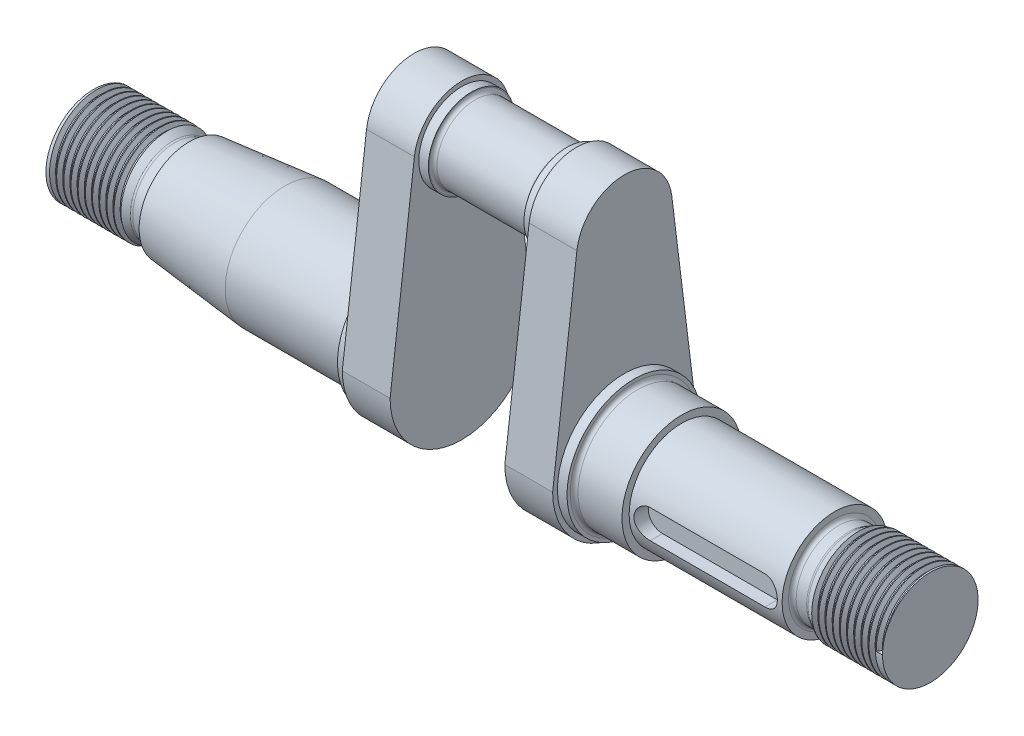
SolidWorks part; units mm, degrees
ref_plane "Ön Düzlem" through (0, 0, 0) normal (0, 0, 1) x (1, 0, 0)
ref_plane "Üst Düzlem" through (0, 0, 0) normal (0, 1, 0) x (1, 0, 0)
ref_plane "Sağ Düzlem" through (0, 0, 0) normal (1, 0, 0) x (0, 0, -1)
sketch "Çizim1" plane through (0, 0, 0) normal (0, 0, 1) x (1, 0, 0)
  line L0 (127.617, 0) -> (-127.617, 0) construction
  line L1 (0, 73.5371) -> (0, -73.5371) construction
  line L2 (-67, 0) -> (-67, 10)
  line L3 (-67, 0) -> (-67, 10)
  line L4 (-67, 10.5) -> (-47, 10.5) construction
  line L5 (-67, 10) -> (-52.2, 10)
  line L6 (-52.2, 10) -> (-50.3938, 8.9572)
  line L7 (-47, 10.5) -> (-47, 9.65)
  line L8 (-49.9938, 8.85) -> (-47.8, 8.85)
  line L9 (-67, 0) -> (0, 0)
  line L10 (-47, 10.5) -> (-27, 12.5)
  line L12 (-27, 12.5) -> (-2.8, 12.5)
  line L13 (0, 14) -> (-2, 14)
  line L14 (-2, 14) -> (-2, 13.3)
  line L15 (0, 14) -> (0, 0)
  arc A0 (-47.8, 8.85) -> (-47, 9.65) centre (-47.8, 9.65) ccw
  arc A1 (-49.9938, 8.85) -> (-50.3938, 8.9572) centre (-49.9938, 9.65) cw
  arc A2 (-2.8, 12.5) -> (-2, 13.3) centre (-2.8, 13.3) ccw
  point P4 (0, 0)
  point P8 (0, 0)
  point P19 (-50.2081, 8.85)
  dimension "D8" = 0.8
  dimension "D9" = 40
  dimension "D14" = 0.8
  dimension "D1" = 10
  dimension "D2" = 67
  dimension "D3" = 10.5
  dimension "D4" = 20
  dimension "D5" = 14.8
  dimension "D6" = 1.15
  dimension "D7" = 150
  dimension "D10" = 12.5
  dimension "D11" = 0.5
  dimension "D12" = 14
  dimension "D13" = 2
revolve "Döndür3" add sketch "Çizim1" angle 360 about L0 region at (-31.5584, 5.7866, 0)
sketch "Çizim2" plane through (0, 0, 0) normal (0, 0, 1) x (1, 0, 0)
  line L0 (0, 0) -> (0, 50)
  line L1 (0, 0) -> (0, -15)
  line L2 (0, -15) -> (10, -15)
  line L3 (10, -15) -> (10, 50)
  line L4 (10, 50) -> (0, 50)
  dimension "D1" = 50
  dimension "D2" = 15
  dimension "D3" = 10
extrude "Yükseklik-Ekstrüzyon1" add sketch "Çizim2" along normal mid plane 30
sketch "Çizim3" plane through (10, 0, 0) normal (1, 0, 0) x (0, 0, -1)
  line L0 (-15, 50) -> (15, 50) construction
  line L1 (15, -15) -> (15, 50) construction
  line L2 (-15, -15) -> (15, -15) construction
  line L3 (-15, -15) -> (-15, 50) construction
  line L4 (-15, 50) -> (15, 50)
  line L5 (15, -15) -> (15, 50)
  line L6 (-15, -15) -> (15, -15)
  line L7 (-15, -15) -> (-15, 50)
  line L8 (-15, 0) -> (15, 0) construction
  line L9 (0, 0) -> (0, 40) construction
  line L10 (-15, 0) -> (-9.9251, 41.2219)
  line L11 (15, 0) -> (9.9251, 41.2219)
  arc A0 (-15, 0) -> (15, 0) centre (0, 0) ccw
  arc A1 (9.9251, 41.2219) -> (-9.9251, 41.2219) centre (0, 40) ccw
  line M2 (15, -15) -> (15, 50)
  line M3 (15, 50) -> (-15, 50)
  line M4 (-15, 50) -> (-15, -15)
  line M5 (-15, -15) -> (15, -15)
  dimension "D1" = 40
  dimension "D2" = 20
extrude "Kes-Ekstrüzyon1" cut sketch "Çizim3" against normal blind 10 contours A1 L4 L10 M4 | A1 L11 L5 M3 | A0 L6 M2 | A0 L7 M5 region at (10, 34.7237, 12.4002) region at (10, 34.7237, -12.4002) region at (10, -11.6495, 11.6495) region at (10, -11.6495, -11.6495)
sketch "Çizim5" plane through (10, 0, 0) normal (1, 0, 0) x (0, 0, -1)
  line L0 (0, 0) -> (0, 40) construction
  dimension "D1" = 40
sketch "Çizim6" plane through (0, 0, 0) normal (0, 0, 1) x (1, 0, 0)
  line L0 (10, 40) -> (34, 40) construction
  line L1 (10, 0) -> (10, 40) construction
  line L2 (10, 0) -> (10, 40) construction
  line L3 (10, 40) -> (10, 49)
  line L4 (10, 49) -> (12, 49)
  line L5 (12, 49) -> (12, 48.8)
  line L6 (12.8, 48) -> (31.2, 48)
  line L7 (22, 40) -> (22, 15.1349) construction
  line L8 (32, 49) -> (32, 48.8)
  line L9 (34, 49) -> (32, 49)
  line L10 (34, 40) -> (34, 49)
  line L12 (10, 40) -> (34, 40)
  arc A0 (12.8, 48) -> (12, 48.8) centre (12.8, 48.8) cw
  arc A1 (31.2, 48) -> (32, 48.8) centre (31.2, 48.8) ccw
  point P10 (12, 48)
  dimension "D6" = 0.8
  dimension "D1" = 12
  dimension "D2" = 9
  dimension "D3" = 2
  dimension "D4" = 1
  dimension "D5" = 12
revolve "Döndür4" add sketch "Çizim6" angle 360 about L12
ref_plane "Düzlem1" through (22, 0, 0) normal (1, 0, 0) x (0, 0, -1)
mirror "Aynalama1" about plane through (22, 0, 0) normal (1, 0, 0) of "Yükseklik-Ekstrüzyon1"
mirror "Aynalama2" about plane through (22, 0, 0) normal (1, 0, 0) of "Kes-Ekstrüzyon1"
sketch "Çizim8" plane through (44, 0, 0) normal (1, 0, 0) x (0, 0, -1)
  line L0 (0, 0) -> (-5.7446, 0) construction
  line L1 (0, 0) -> (0, -4.8155) construction
sketch "Çizim9" plane through (0, 0, 0) normal (0, 0, 1) x (1, 0, 0)
  line L0 (44, 0) -> (44, -4.8155) construction
  line L1 (44, 0) -> (44, -4.8155) construction
  line L2 (44, 0) -> (44, 14)
  line L3 (44, 0) -> (96.3723, 0) construction
  line L4 (44, 14) -> (46, 14)
  line L5 (46, 0) -> (46, 12.5) construction
  line L6 (46, 14) -> (46, 13.3)
  line L7 (46.8, 12.5) -> (56, 12.5)
  line L8 (56, 0) -> (56, 11) construction
  line L9 (56, 12.5) -> (56, 11)
  line L10 (56, 11) -> (88, 11)
  line L11 (88, 11) -> (88, 0)
  line L12 (44, 0) -> (88, 0)
  arc A0 (46, 13.3) -> (46.8, 12.5) centre (46.8, 13.3) ccw
  dimension "D5" = 0.8
  dimension "D1" = 14
  dimension "D2" = 2
  dimension "D3" = 12.5
  dimension "D4" = 10
  dimension "D6" = 11
  dimension "D7" = 32
revolve "Döndür5" add sketch "Çizim9" angle 360 about L12
sketch "Çizim10" plane through (0, 0, 0) normal (0, 0, 1) x (1, 0, 0)
  line L0 (88, -11) -> (88, 11) construction
  line L1 (88, -11) -> (88, 0) construction
  line L2 (88, 11) -> (108, 11) construction
  line L3 (88, 10) -> (108, 10) construction
  line L4 (44, 0) -> (108, 0) construction
  line L5 (108, 0) -> (108, 10)
  line L6 (108, 10) -> (93.2, 10)
  line L7 (93.2, 10) -> (91.3938, 8.9572)
  line L8 (90.9938, 8.85) -> (88.8, 8.85)
  line L9 (88, 9.65) -> (88, 10)
  line L10 (88, 10) -> (88, 9.65)
  line L11 (88, 9.65) -> (88, 10) construction
  line L12 (88, -11) -> (88, 10)
  line L13 (88, 0) -> (108, 0)
  arc A0 (88, 9.65) -> (88.8, 8.85) centre (88.8, 9.65) ccw
  arc A1 (90.9938, 8.85) -> (91.3938, 8.9572) centre (90.9938, 9.65) ccw
  point P15 (88, 8.85)
  point P18 (91.2081, 8.85)
  dimension "D7" = 0.8
  dimension "D1" = 20
  dimension "D2" = 1
  dimension "D3" = 10
  dimension "D4" = 14.8
  dimension "D5" = 150
  dimension "D6" = 1.15
revolve "Döndür6" add sketch "Çizim10" angle 360 about L4 region at (98.1875, 4.8922, 0)
ref_plane "Düzlem2" through (0, 0, 11) normal (0, 0, 1) x (1, 0, 0)
sketch "Çizim11" plane through (0, 0, 11) normal (0, 0, 1) x (1, 0, 0)
  line L0 (84, 0) -> (60, 0) construction
  line L1 (44, 0) -> (44, -4.8155) construction
  line L2 (44, 0) -> (44, -4.8155) construction
  line L3 (44, 0) -> (88, 0) construction
  line L4 (88, -11) -> (88, 11) construction
  line L5 (84, -3) -> (60, -3)
  line L6 (84, 3) -> (60, 3)
  line L7 (56, -12.5) -> (56, 12.5) construction
  arc A0 (84, -3) -> (84, 3) centre (84, 0) ccw
  arc A1 (60, 3) -> (60, -3) centre (60, 0) ccw
  point P7 (72, 0)
  dimension "D1" = 4
  dimension "D2" = 6
  dimension "D3" = 24
extrude "Kes-Ekstrüzyon2" cut sketch "Çizim11" against normal blind 3
mirror "Aynalama3" about plane through (0, 0, 0) normal (0, 0, 1) of "Kes-Ekstrüzyon2"
thread "Diş1" pitch 1.5 method cut profile "Diş Profili1" start angle 0, offset 0, length 0, pitch 1.5, diameter 20
ref_plane "Düzlem3" through (-67, 0, -10) normal (0, -1, 0) x (0, 0, -1)
sketch "Diş Profili1" plane through (-67, 0, -10) normal (0, -1, 0) x (0, 0, -1)
  line L0 (0, 0) -> (0, 1.5) construction
  line L11 (0, 0) -> (0, 1.3125)
  line L12 (0, 1.3125) -> (-0.8119, 0.8437)
  line L13 (-0.8119, 0.8437) -> (-0.8119, 0.4687)
  line L15 (-0.8119, 0.4687) -> (0, 0)
  line L17 (-0.8119, 0.6562) -> (0, 0.6562) construction
  point P2 (0, 0)
  dimension "Pitch" = 1.5
  dimension "Profile_Angle" = 60
  dimension "Profile_Land" = 0.375
  dimension "Profile_Height" = 0.8119
thread "Diş2" pitch 1.5 method cut profile "Diş Profili2" start angle 0, offset 0, length 0, pitch 1.5, diameter 20
ref_plane "Düzlem4" through (108, 0, 10) normal (0, -1, 0) x (0, 0, 1)
sketch "Diş Profili2" plane through (108, 0, 10) normal (0, -1, 0) x (0, 0, 1)
  line L0 (0, 0) -> (0, 1.5) construction
  line L11 (0, 0) -> (0, 1.3125)
  line L12 (0, 1.3125) -> (-0.8119, 0.8437)
  line L13 (-0.8119, 0.8437) -> (-0.8119, 0.4687)
  line L15 (-0.8119, 0.4687) -> (0, 0)
  line L17 (-0.8119, 0.6562) -> (0, 0.6562) construction
  point P2 (0, 0)
  dimension "Pitch" = 1.5
  dimension "Profile_Angle" = 60
  dimension "Profile_Land" = 0.375
  dimension "Profile_Height" = 0.8119
